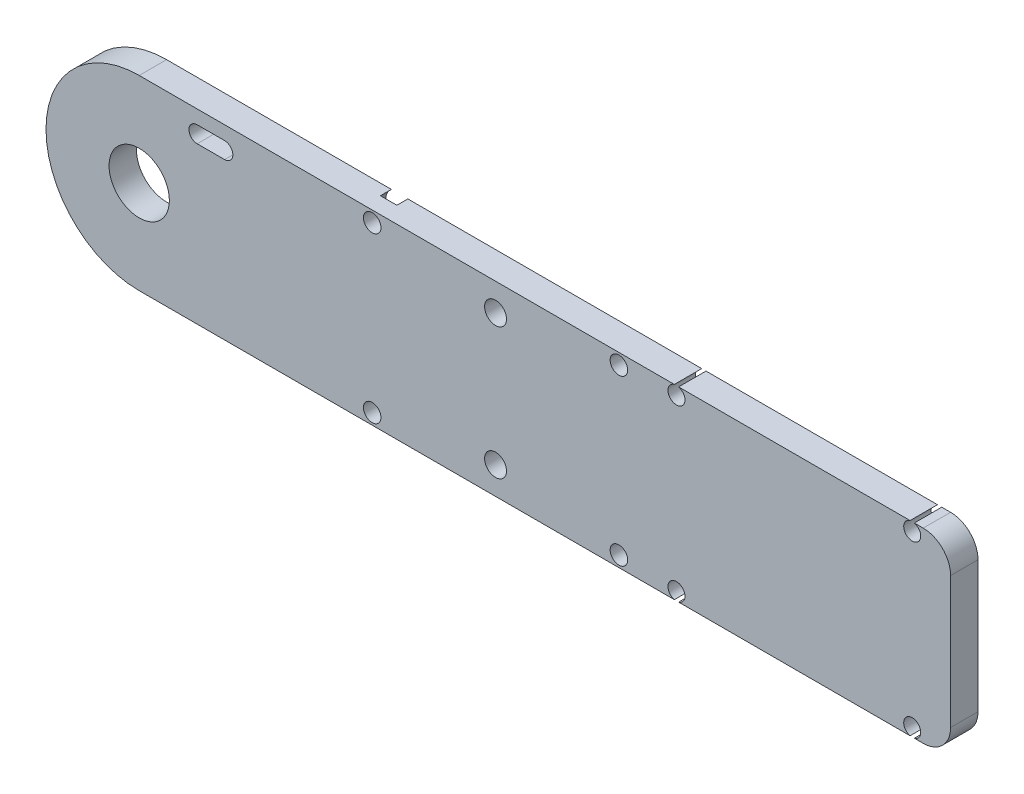
SolidWorks part; units mm, degrees
material "Acrylic (Medium-high impact)"
ref_plane "Front Plane" through (0, 0, 0) normal (0, 0, 1) x (1, 0, 0)
ref_plane "Top Plane" through (0, 0, 0) normal (0, 1, 0) x (1, 0, 0)
ref_plane "Right Plane" through (0, 0, 0) normal (1, 0, 0) x (0, 0, -1)
sketch "Sketch2" plane through (0, 0, 0) normal (0, 0, 1) x (1, 0, 0)
  line L0 (0, 17) -> (0, -17)
  line L1 (0, 17) -> (148, 17)
  line L2 (0, -17) -> (148, -17)
  line L3 (148, 17) -> (148, -17)
  line L4 (0, 0) -> (-17, 0)
  circle A0 centre (0, 0) radius 17
  circle A1 centre (0, 0) radius 5.5
  dimension "D1" = 34
  dimension "D3" = 11
  dimension "D2" = 165
extrude "Boss-Extrude1" add sketch "Sketch2" along normal mid plane 5 contours A1 L0 A0 | A0 L2 L3 L1 | A1 L4 A0 L0 | A1 L0 A0 L4 region at (7.7856, 0, 0) region at (80.6224, 0, 0) region at (-7.7856, 7.7856, 0) region at (-7.7856, -7.7856, 0)
fillet "Fillet1" radius 5 2 edges at (148, -17, 0) (148, 17, 0)
sketch "Sketch3" plane through (0, 0, -2.5) normal (0, 0, -1) x (-1, 0, 0)
  line L0 (-119.5, 17) -> (-119.5, -17)
  line L1 (-119.5, 0) -> (-98, 0)
  line L2 (-98, 0) -> (-98, 15.5)
  line L3 (-148, 12) -> (-148, -12)
  line L4 (-143, -17) -> (0, -17)
  line L5 (0, 17) -> (-143, 17)
  line L6 (-148, 12) -> (-148, -12)
  line L7 (-143, -17) -> (0, -17)
  line L8 (0, 17) -> (-143, 17)
  line L9 (-119.5, 0) -> (-65, 0)
  line L10 (-65, 0) -> (-65, 15)
  line L11 (-65, 15) -> (-87.5, 15)
  line L12 (0, 0) -> (0, 12)
  line L13 (0, 0) -> (-65, 0)
  line L14 (-15.5742, 13) -> (-10.5742, 13) construction
  line L17 (-15.5742, 14.5) -> (-10.5742, 14.5)
  line L18 (-15.5742, 11.5) -> (-10.5742, 11.5)
  line L19 (0, 0) -> (18.4819, 0)
  line L20 (-65, 0.6163) -> (-65, 6.1951)
  line L21 (-65, 0) -> (-65, 12)
  circle A0 centre (0, 0) radius 12
  circle A1 centre (-98, 15.5) radius 1.55
  circle A2 centre (-98, -15.5) radius 1.55
  arc A3 (-148, -12) -> (-143, -17) centre (-143, -12) ccw
  arc A4 (0, -17) -> (0, 17) centre (0, 0) ccw
  arc A5 (-143, 17) -> (-148, 12) centre (-143, 12) ccw
  arc A6 (-148, -12) -> (-143, -17) centre (-143, -12) ccw
  arc A7 (0, -17) -> (0, 17) centre (0, 0) ccw
  arc A8 (-143, 17) -> (-148, 12) centre (-143, 12) ccw
  circle A9 centre (-141, -15.5) radius 1.55
  circle A10 centre (-141, 15.5) radius 1.55
  circle A11 centre (-87.5, 15) radius 1.6
  circle A12 centre (-87.5, -15) radius 1.6
  circle A13 centre (-42.5, -15) radius 1.6
  circle A14 centre (-42.5, 15) radius 1.6
  circle A15 centre (0, 12) radius 2.1
  circle A16 centre (12, 0) radius 2.1
  circle A17 centre (-7.6279, -12) radius 2.1
  circle A18 centre (-12, 0) radius 2.1
  arc A21 (-15.5742, 14.5) -> (-15.5742, 11.5) centre (-15.5742, 13) ccw
  arc A22 (-10.5742, 11.5) -> (-10.5742, 14.5) centre (-10.5742, 13) ccw
  circle A23 centre (-65, 12) radius 2
  circle A25 centre (-65, -12) radius 2
  point P35 (-13.0742, 13)
  point P48 (12, 0)
  point P53 (-12, 0)
  point P54 (-7.6279, -12)
  point P59 (0, 0)
  point P60 (0, 0)
  point P61 (0, 0)
  dimension "D2" = 24
  dimension "D6" = 3.1
  dimension "D10" = 3.2
  dimension "D11" = 4.2
  dimension "D13" = 65
  dimension "D17" = 65
  dimension "D18" = 4.2
  dimension "D12" = 4.2
  dimension "D19" = 4.2
  dimension "D21" = 4
  dimension "D3" = 21.5
  dimension "D4" = 15.5
  dimension "D5" = 98
  dimension "D7" = 27
  dimension "D8" = 15
  dimension "D9" = 22.5
  dimension "D14" = 5
  dimension "D15" = 3
  dimension "D16" = 4
  dimension "D20" = 12
  dimension "D1" = 0
extrude "Cut-Extrude1" cut sketch "Sketch3" against normal through all contours L18 A22 L17 A21 | L10 A23 L21 | L21 A23 L10 | A25 | A11 | A12 | A2 | A1 | A10 | A9 region at (98, 16.9565, -2.5) region at (141, 15.4947, -2.5) region at (89.0547, 15, -2.5) region at (65.8488, 12, -2.5) region at (64.1512, 12, -2.5) region at (141, -15.4947, -2.5) region at (98, -15.4947, -2.5) region at (13.0742, 13, -2.5) region at (87.5, -15, -2.5) region at (65, -12, -2.5)
extrude "Cut-Extrude2" cut sketch "Sketch3<4>" against normal blind 10 contours L18 A22 L17 A21 | A12 | A11 | A13 | A14 | A10 | A9 | A1 | A2 | L21 A23 L10 | L10 A23 L21 | A25 region at (98, 16.9565, -2.5) region at (141, 15.4947, -2.5) region at (89.0547, 15, -2.5) region at (65.8488, 12, -2.5) region at (64.1512, 12, -2.5) region at (141, -15.4947, -2.5) region at (98, -15.4947, -2.5) region at (13.0742, 13, -2.5) region at (87.5, -15, -2.5) region at (42.5, -15, -2.5) region at (42.5, 15, -2.5) region at (65, -12, -2.5)
sketch "Sketch3<4>" plane through (0, 0, -2.5) normal (0, 0, -1) x (-1, 0, 0) same geometry as "Sketch3"
sketch "Sketch4" plane through (0, 0, -2.5) normal (0, 0, -1) x (-1, 0, 0)
  circle A0 centre (-42.5, 15) radius 2.5
  circle A1 centre (-42.5, -15) radius 2.5
  dimension "D1" = 5
  dimension "D2" = 5
extrude "Cut-Extrude3" cut sketch "Sketch4" against normal blind 2
